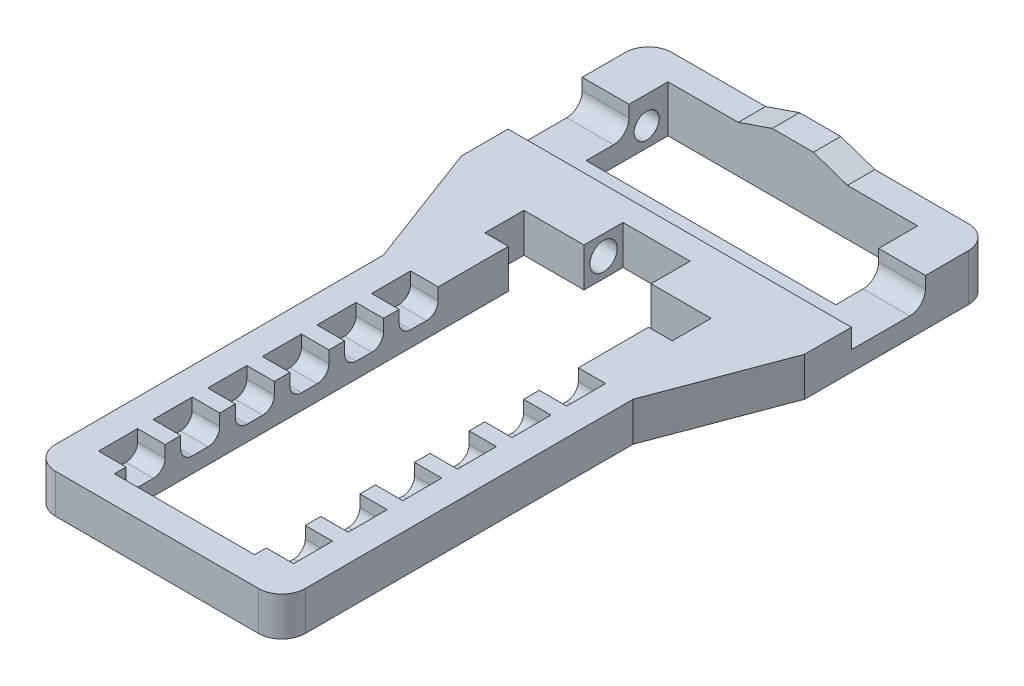
SolidWorks part; units mm, degrees
ref_plane "Front Plane" through (0, 0, 0) normal (0, 0, 1) x (1, 0, 0)
ref_plane "Top Plane" through (0, 0, 0) normal (0, 1, 0) x (1, 0, 0)
ref_plane "Right Plane" through (0, 0, 0) normal (1, 0, 0) x (0, 0, -1)
sketch "Sketch1" plane through (0, 0, 0) normal (0, 1, 0) x (1, 0, 0)
  line L0 (-22, -2) -> (22, -2)
  line L1 (-22, 20) -> (22, 20)
  line L2 (-22, 20) -> (-22, -63)
  line L3 (-22, -63) -> (22, -63)
  line L4 (22, 20) -> (22, -63)
  line L5 (-16, -63) -> (16, -63)
  line L6 (-16, -63) -> (-16, -18)
  line L7 (-16, -18) -> (16, -18)
  line L8 (16, -63) -> (16, -18)
  line L9 (-22, -2) -> (-16, -18)
  line L10 (16, -18) -> (22, -2)
  line L12 (-12.5, -18) -> (12.5, -18)
  line L13 (-12.5, -18) -> (-12.5, -59.5)
  line L14 (-12.5, -59.5) -> (12.5, -59.5)
  line L15 (12.5, -18) -> (12.5, -59.5)
  dimension "D1" = 22
  dimension "D2" = 44
  dimension "D3" = 20
  dimension "D4" = 83
  dimension "D5" = 32
  dimension "D6" = 6
  dimension "D7" = 45
  dimension "D8" = 22
  dimension "D9" = 3.5
  dimension "D10" = 3.5
  dimension "D11" = 3.5
extrude "Boss-Extrude1" add sketch "Sketch1" along normal blind 5 contours L4 L1 L2 L0 | L7 L10 L0 L9 | L7 L15 L14 L13 L6 L3 L8
sketch "Sketch2" plane through (0, 0, 0) normal (0, -1, 0) x (1, 0, 0)
  line L1 (-12.5, 18) -> (12.5, 18)
  line L2 (-12.5, 18) -> (-12.5, 59.5)
  line L3 (-12.5, 59.5) -> (12.5, 59.5)
  line L4 (12.5, 18) -> (12.5, 59.5)
  line L5 (-8.9681, 18) -> (9, 18)
  line L6 (-8.9681, 18) -> (-8.9681, 59.5)
  line L7 (-8.9681, 59.5) -> (9, 59.5)
  line L8 (9, 18) -> (9, 59.5)
  line M8 (-12.5, 18) -> (-12.5, 59.5)
  line M9 (-12.5, 59.5) -> (12.5, 59.5)
  line M10 (12.5, 59.5) -> (12.5, 18)
  line M11 (12.5, 18) -> (-12.5, 18)
  dimension "D1" = 3.5319
  dimension "D2" = 3.5
  dimension "D3" = 0
extrude "Boss-Extrude2" add sketch "Sketch2" against normal blind 2 contours L6 M11 M9 M8 | L8 M11 M10 M9 | L4 L3 L2 L1
sketch "Sketch3" plane through (0, 5, 0) normal (0, 1, 0) x (1, 0, 0)
  line L0 (-22, 20) -> (-22, -2) construction
  line L1 (-22, 13.5) -> (22, 13.5)
  line L2 (-22, 13.5) -> (-22, 4)
  line L3 (-22, 4) -> (22, 4)
  line L4 (22, 13.5) -> (22, 4)
  line L5 (22, 20) -> (22, -2) construction
  line L6 (-22, 20) -> (22, 20) construction
  dimension "D1" = 9.5
  dimension "D2" = 6.5
extrude "Cut-Extrude1" cut sketch "Sketch3" against normal blind 2.5
sketch "Sketch4" plane through (0, 5, 0) normal (0, 1, 0) x (1, 0, 0)
  line L0 (-12.5, -18) -> (12.5, -18) construction
  line L1 (-8.9681, -18) -> (9, -18)
  line L2 (-8.9681, -18) -> (-8.9681, -4)
  line L3 (-8.9681, -4) -> (9, -4)
  line L4 (9, -18) -> (9, -4)
  line L5 (9, -18) -> (9, -59.5) construction
  line L6 (-8.9681, -18) -> (-8.9681, -59.5) construction
  dimension "D1" = 0
  dimension "D2" = 0
  dimension "D3" = 14
extrude "Cut-Extrude2" cut sketch "Sketch4" against normal blind 5
sketch "Sketch5" plane through (0, 5, 0) normal (0, 1, 0) x (1, 0, 0)
  line L0 (-8.9681, -4) -> (-8.9681, -18) construction
  line L1 (-11.9681, -4) -> (12.0319, -4)
  line L2 (-11.9681, -4) -> (-11.9681, -9)
  line L3 (-11.9681, -9) -> (12.0319, -9)
  line L4 (12.0319, -4) -> (12.0319, -9)
  line L7 (-12.5, -18) -> (-8.9681, -18) construction
  line L8 (9, -4) -> (-8.9681, -4) construction
  dimension "D1" = 24
  dimension "D2" = 3
  dimension "D3" = 9
  dimension "D4" = 0
extrude "Cut-Extrude3" cut sketch "Sketch5" against normal blind 5
sketch "Sketch6" plane through (0, 5, 0) normal (0, 1, 0) x (1, 0, 0)
  line L0 (12.0319, -4) -> (-11.9681, -4) construction
  line L1 (-4.2681, -4) -> (4.3319, -4)
  line L2 (-4.2681, -4) -> (-4.2681, 1)
  line L3 (-4.2681, 1) -> (4.3319, 1)
  line L4 (4.3319, -4) -> (4.3319, 1)
  line L5 (12.0319, -9) -> (12.0319, -4) construction
  line L6 (-11.9681, -4) -> (-11.9681, -9) construction
  dimension "D1" = 7.7
  dimension "D2" = 8.6
  dimension "D3" = 7.7
  dimension "D4" = 5
extrude "Cut-Extrude4" cut sketch "Sketch6" against normal blind 5
sketch "Sketch7" plane through (0, 5, 0) normal (0, 1, 0) x (1, 0, 0)
  line L0 (-22, 20) -> (22, 20) construction
  line L1 (-7, 20) -> (7, 20)
  line L2 (-7, 20) -> (-7, 18)
  line L3 (-7, 18) -> (7, 18)
  line L4 (7, 20) -> (7, 18)
  line L5 (22, 20) -> (22, 13.5) construction
  line L6 (-22, 20) -> (-22, 13.5) construction
  dimension "D1" = 2
  dimension "D2" = 15
  dimension "D3" = 15
extrude "Boss-Extrude3" add sketch "Sketch7" along normal blind 1.5
chamfer "Chamfer1" distance 1.5 angle 71 2 edges at (7, 6.5, -19) (-7, 6.5, -19)
sketch "Sketch8" plane through (0, 5, 0) normal (0, 1, 0) x (1, 0, 0)
  line L0 (-7, 18) -> (7, 18) construction
  line L1 (-16, 18) -> (16, 18)
  line L2 (-16, 18) -> (-16, 8)
  line L3 (-16, 8) -> (16, 8)
  line L4 (16, 18) -> (16, 8)
  line L5 (22, 20) -> (22, 13.5) construction
  line L6 (-22, 20) -> (-22, 13.5) construction
  dimension "D1" = 0
  dimension "D2" = 6
  dimension "D3" = 6
  dimension "D4" = 10
extrude "Cut-Extrude5" cut sketch "Sketch8" against normal blind 5
fillet "Fillet3" radius 3 2 edges at (-16, 2.5, 63) (16, 2.5, 63)
sketch "Sketch9" plane through (-4.2681, 0, 0) normal (1, 0, 0) x (0, 0, -1)
  circle A0 centre (-1.5, 2.5) radius 1.75
  dimension "D1" = 3.5
extrude "Cut-Extrude6" cut sketch "Sketch9" against normal blind 3
sketch "Sketch10" plane through (4.3319, 0, 0) normal (-1, 0, 0) x (0, 0, 1)
  circle A0 centre (1.5, 2.5) radius 1.75
  dimension "D1" = 3.5
extrude "Cut-Extrude7" cut sketch "Sketch10" against normal blind 3
sketch "Sketch11" plane through (16, 0, 0) normal (-1, 0, 0) x (0, 0, 1)
  line L0 (-13.5, 5) -> (-18, 5) construction
  line L1 (-18, 0) -> (-18, 5) construction
  circle A0 centre (-15.75, 2.5) radius 1.6
  dimension "D1" = 3.2
  dimension "D2" = 2.5
  dimension "D3" = 2.25
extrude "Cut-Extrude8" cut sketch "Sketch11" against normal blind 3
sketch "Sketch12" plane through (-16, 0, 0) normal (1, 0, 0) x (0, 0, -1)
  line L0 (18, 5) -> (13.5, 5) construction
  line L1 (18, 0) -> (18, 5) construction
  circle A0 centre (15.75, 2.5) radius 1.6
  dimension "D1" = 2.5
  dimension "D2" = 2.25
  dimension "D3" = 3.2
extrude "Cut-Extrude9" cut sketch "Sketch12" against normal blind 3
sketch "Sketch13" plane through (0, 2, 0) normal (0, 1, 0) x (1, 0, 0)
  line L0 (-8.9681, -18) -> (-8.9681, -59.5) construction
  line L1 (-8.9681, -23) -> (-12.5, -23)
  line L2 (-8.9681, -23) -> (-8.9681, -25)
  line L3 (-8.9681, -25) -> (-12.5, -25)
  line L4 (-12.5, -23) -> (-12.5, -25)
  line L5 (-12.5, -18) -> (-12.5, -59.5) construction
  line L6 (-8.9681, -18) -> (-12.5, -18) construction
  line L7 (12.5319, -23) -> (12.5319, -25)
  line L8 (12.5319, -23) -> (9, -23)
  line L9 (9, -23) -> (9, -25)
  line L10 (12.5319, -25) -> (9, -25)
  line L11 (12.5319, -30) -> (12.5319, -32)
  line L12 (12.5319, -30) -> (9, -30)
  line L13 (9, -30) -> (9, -32)
  line L14 (12.5319, -32) -> (9, -32)
  line L15 (12.5319, -37) -> (12.5319, -39)
  line L16 (12.5319, -37) -> (9, -37)
  line L17 (9, -37) -> (9, -39)
  line L18 (12.5319, -39) -> (9, -39)
  line L19 (12.5319, -44) -> (12.5319, -46)
  line L20 (12.5319, -44) -> (9, -44)
  line L21 (9, -44) -> (9, -46)
  line L22 (12.5319, -46) -> (9, -46)
  line L23 (12.5319, -51) -> (12.5319, -53)
  line L24 (12.5319, -51) -> (9, -51)
  line L25 (9, -51) -> (9, -53)
  line L26 (12.5319, -53) -> (9, -53)
  line L27 (12.5319, -58) -> (12.5319, -60)
  line L28 (12.5319, -58) -> (9, -58)
  line L29 (9, -58) -> (9, -60)
  line L30 (12.5319, -60) -> (9, -60)
  line L31 (-8.9681, -30) -> (-8.9681, -32)
  line L32 (-8.9681, -30) -> (-12.5, -30)
  line L33 (-12.5, -30) -> (-12.5, -32)
  line L34 (-8.9681, -32) -> (-12.5, -32)
  line L35 (-8.9681, -37) -> (-8.9681, -39)
  line L36 (-8.9681, -37) -> (-12.5, -37)
  line L37 (-12.5, -37) -> (-12.5, -39)
  line L38 (-8.9681, -39) -> (-12.5, -39)
  line L39 (-8.9681, -44) -> (-8.9681, -46)
  line L40 (-8.9681, -44) -> (-12.5, -44)
  line L41 (-12.5, -44) -> (-12.5, -46)
  line L42 (-8.9681, -46) -> (-12.5, -46)
  line L43 (-8.9681, -51) -> (-8.9681, -53)
  line L44 (-8.9681, -51) -> (-12.5, -51)
  line L45 (-12.5, -51) -> (-12.5, -53)
  line L46 (-8.9681, -53) -> (-12.5, -53)
  line L47 (-8.9681, -58) -> (-8.9681, -60)
  line L48 (-8.9681, -58) -> (-12.5, -58)
  line L49 (-12.5, -58) -> (-12.5, -60)
  line L50 (-8.9681, -60) -> (-12.5, -60)
  dimension "D1" = 5
  dimension "D2" = 2
  dimension "D3" = 2
  dimension "D4" = 6
extrude "Boss-Extrude5" add sketch "Sketch13" along normal blind 3
fillet "Fillet4" radius 1.5 24 edges at (10.75, 2, 18) (10.75, 2, 25) (10.75, 2, 32) (10.75, 2, 39) (10.75, 2, 23) (10.75, 2, 30) (10.75, 2, 37) (10.75, 2, 44) (10.75, 2, 46) (10.75, 2, 51) (10.75, 2, 53) (10.75, 2, 58) (-10.734, 2, 18) (-10.734, 2, 23) (-10.734, 2, 25) (-10.734, 2, 30) (-10.734, 2, 32) (-10.734, 2, 37) (-10.734, 2, 39) (-10.734, 2, 44) (-10.734, 2, 46) (-10.734, 2, 51) (-10.734, 2, 53) (-10.734, 2, 58)
sketch "Sketch14" plane through (0, 0, -20) normal (0, 0, -1) x (-1, 0, 0)
  line L0 (-22, 6) -> (-22, 0)
  line L1 (-22, 0) -> (22, 0)
  line L2 (22, 0) -> (22, 6)
  line L3 (22, 6) -> (7, 6)
  line L4 (7, 6) -> (2.6437, 7.5)
  line L5 (2.6437, 7.5) -> (-2.6437, 7.5)
  line L6 (-2.6437, 7.5) -> (-7, 6)
  line L7 (-7, 6) -> (-22, 6)
  point P8 (0, 0)
  point P13 (0, 0)
  dimension "D1" = 6
  dimension "D2" = 1
  dimension "D3" = 1
  dimension "D4" = 0
  dimension "D5" = 1
  dimension "D6" = 1
  dimension "D7" = 7.5
extrude "Boss-Extrude6" add sketch "Sketch14" along normal blind 2 and the other way blind 2
sketch "Sketch15" plane through (0, 0, -18) normal (0, 0, 1) x (1, 0, 0)
  line L0 (22, 5) -> (16, 5) construction
  line L1 (16, 5) -> (22, 5)
  line L2 (16, 5) -> (16, 6)
  line L3 (16, 6) -> (22, 6)
  line L4 (22, 5) -> (22, 6)
  line L6 (-22, 6) -> (-16, 6)
  line L7 (-22, 6) -> (-22, 5)
  line L8 (-22, 5) -> (-16, 5)
  line L9 (-16, 6) -> (-16, 5)
extrude "Boss-Extrude7" add sketch "Sketch15" along normal blind 4.5
fillet "Fillet5" radius 2 1 edges at (-19, 2.5, -13.5)
fillet "Fillet6" radius 3 2 edges at (22, 3, -22) (-22, 3, -22)
sketch "Sketch16" plane through (0, 6, 0) normal (0, 1, 0) x (1, 0, 0)
  line L1 (-16, 18) -> (16, 18)
  line L2 (-16, 18) -> (-16, 18.5)
  line L3 (-16, 18.5) -> (16, 18.5)
  line L4 (16, 18) -> (16, 18.5)
  dimension "D1" = 0.5
extrude "Cut-Extrude10" cut sketch "Sketch16" against normal blind 14.5 and the other way blind 14.5
